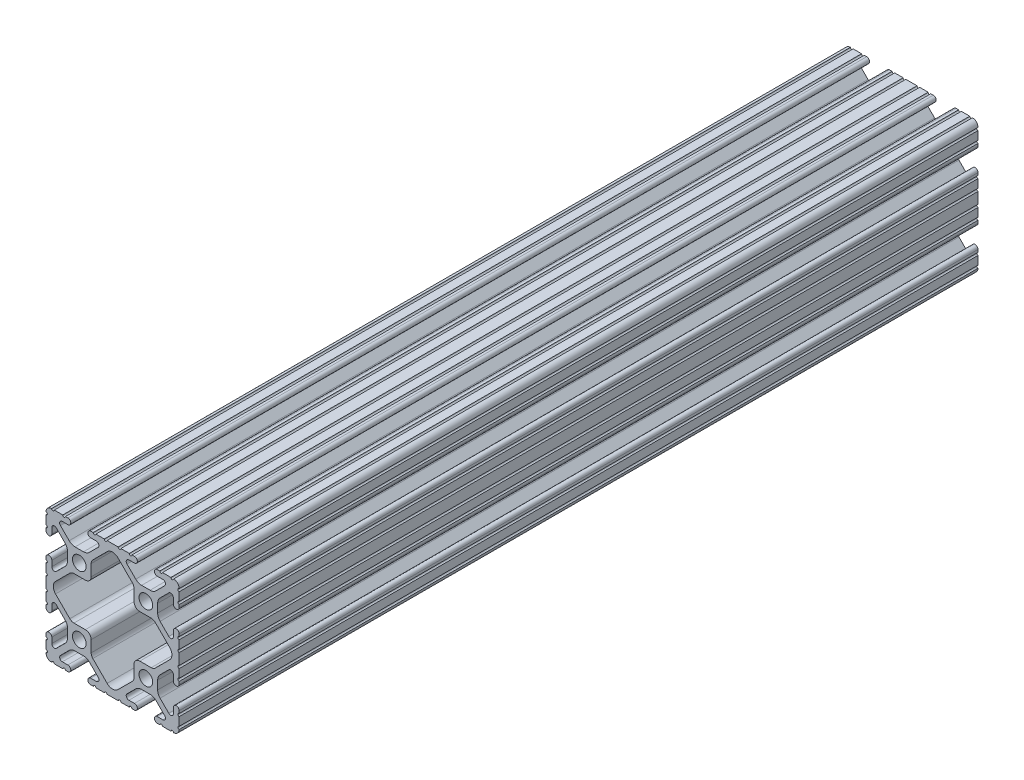
SolidWorks part; units mm, degrees
ref_plane "Front Plane" through (0, 0, 0) normal (0, 0, 1) x (1, 0, 0)
ref_plane "Top Plane" through (0, 0, 0) normal (0, 1, 0) x (1, 0, 0)
ref_plane "Right Plane" through (0, 0, 0) normal (1, 0, 0) x (0, 0, -1)
sketch "Sketch1" plane through (0, 0, 0) normal (0, 0, 1) x (1, 0, 0)
  line L0 (-25.4, 0) -> (25.4, 0) construction
  line L1 (0, 25.4) -> (0, -25.4) construction
  line L2 (-12.7, 12.7) -> (-25.4, 25.4) construction
  line L3 (-25.4, 23.8374) -> (-15.1482, 13.5857) construction
  line L4 (-23.8374, 25.4) -> (-13.5857, 15.1482) construction
  line L5 (9.4488, 25.4) -> (15.9512, 25.4) construction
  line L6 (12.7, 25.4) -> (12.7, 17.1958) construction
  line L7 (5.2832, 23.1902) -> (20.1168, 23.1902) construction
  circle A0 centre (-12.7, 12.7) radius 2.6035 construction
  circle A1 centre (12.7, 12.7) radius 2.6035 construction
  circle A2 centre (12.7, -12.7) radius 2.6035 construction
  circle A3 centre (-12.7, -12.7) radius 2.6035 construction
  circle A4 centre (0, 0) radius 12.4841 construction
  point P4 (0, 0)
  point P8 (0, 0)
  point P26 (12.7, 25.4)
  point P28 (12.7, 23.1902)
  dimension "Center Hole Diameter" = 5.207
  dimension "D5" = 24.9682
  dimension "Rail Width" = 50.8
  dimension "Rail Height" = 50.8
  dimension "D1" = 25.4
  dimension "D2" = 25.4
  dimension "D3" = 2.2098
  dimension "T Slot Width" = 6.5024
  dimension "T Slot Depth" = 8.2042
  dimension "Thickness" = 2.2098
  dimension "D4" = 14.8336
sketch "Sketch2" plane through (0, 0, 0) normal (1, 0, 0) x (0, 0, -1)
  line L0 (152.4, 0) -> (-152.4, 0)
  point P0 (-101.6, 0)
  point P4 (0, 0)
  point P5 (101.6, 0)
  point P6 (152.4, 25.4)
  point P7 (-152.4, 25.4)
  dimension "Length" = 304.8
  dimension "D2" = 50.8
sketch "Sketch3" plane through (0, 0, 0) normal (0, 0, 1) x (1, 0, 0)
  line L0 (-25.4, 0) -> (-25.4, 8.3439)
  line L2 (-23.1902, 8.3439) -> (-23.1902, 6.2252)
  line L3 (-21.4558, 5.5068) -> (-18.1257, 8.8368)
  line L4 (-17.1958, 11.0819) -> (-17.1958, 14.3181)
  line L5 (-18.1257, 16.5632) -> (-21.4558, 19.8932)
  line L6 (-23.1902, 19.1748) -> (-23.1902, 17.0561)
  line L8 (-25.4, 17.0561) -> (-25.4, 23.2918)
  line L9 (-23.2918, 25.4) -> (-17.0561, 25.4)
  line L11 (-17.0561, 23.1902) -> (-19.1748, 23.1902)
  line L12 (-19.8932, 21.4558) -> (-16.5632, 18.1257)
  line L13 (-14.3181, 17.1958) -> (-11.0819, 17.1958)
  line L14 (-8.8368, 18.1257) -> (-5.5068, 21.4558)
  line L15 (-6.2252, 23.1902) -> (-8.3439, 23.1902)
  line L17 (-8.3439, 25.4) -> (0, 25.4)
  line L18 (0, 25.4) -> (0, 22.6275)
  line L19 (-2.0655, 21.772) -> (-7.5331, 16.3043)
  line L20 (-8.1804, 14.7417) -> (-8.1804, 10.3902)
  line L21 (-10.3902, 8.1804) -> (-14.7417, 8.1804)
  line L22 (-16.3043, 7.5331) -> (-21.772, 2.0655)
  line L23 (-22.6275, 0) -> (-25.4, 0)
  line L24 (0, 25.4) -> (0, -25.4) construction
  line L25 (-12.7, 12.7) -> (-25.4, 25.4) construction
  line L26 (-25.4, 0) -> (25.4, 0) construction
  line L27 (5.2832, 23.1902) -> (20.1168, 23.1902) construction
  line L28 (-9.4488, 24.2951) -> (-15.9512, 24.2951) construction
  line L30 (9.4488, 25.4) -> (15.9512, 25.4) construction
  line L31 (-23.8374, 25.4) -> (-13.5857, 15.1482) construction
  line L32 (-25.4, 23.8374) -> (-15.1482, 13.5857) construction
  arc A0 (-7.5331, 16.3043) -> (-8.1804, 14.7417) centre (-5.9706, 14.7417) ccw
  circle A1 centre (-12.7, 12.7) radius 2.6035 construction
  circle A2 centre (-12.7, 12.7) radius 2.6035
  arc A3 (-8.1804, 10.3902) -> (-10.3902, 8.1804) centre (-10.3902, 10.3902) cw
  arc A4 (-14.7417, 8.1804) -> (-16.3043, 7.5331) centre (-14.7417, 5.9706) ccw
  arc A5 (-21.772, 2.0655) -> (-22.6275, 0) centre (-19.7065, 0) ccw
  arc A6 (0, 22.6275) -> (-2.0655, 21.772) centre (0, 19.7065) ccw
  circle A7 centre (0, 0) radius 12.4841 construction
  arc A8 (-17.0561, 23.1902) -> (-17.0561, 25.4) centre (-17.0561, 24.2951) ccw
  arc A9 (-8.3439, 25.4) -> (-8.3439, 23.1902) centre (-8.3439, 24.2951) ccw
  arc A10 (-25.4, 17.0561) -> (-23.1902, 17.0561) centre (-24.2951, 17.0561) ccw
  arc A11 (-23.1902, 8.3439) -> (-25.4, 8.3439) centre (-24.2951, 8.3439) ccw
  arc A12 (-25.4, 23.2918) -> (-23.2918, 25.4) centre (-23.2918, 23.2918) cw
  arc A13 (-5.5068, 21.4558) -> (-6.2252, 23.1902) centre (-6.2252, 22.1742) ccw
  arc A14 (-19.1748, 23.1902) -> (-19.8932, 21.4558) centre (-19.1748, 22.1742) ccw
  arc A15 (-21.4558, 19.8932) -> (-23.1902, 19.1748) centre (-22.1742, 19.1748) ccw
  arc A16 (-21.4558, 5.5068) -> (-23.1902, 6.2252) centre (-22.1742, 6.2252) cw
  arc A17 (-8.8368, 18.1257) -> (-11.0819, 17.1958) centre (-11.0819, 20.3708) cw
  arc A18 (-14.3181, 17.1958) -> (-16.5632, 18.1257) centre (-14.3181, 20.3708) cw
  arc A19 (-18.1257, 16.5632) -> (-17.1958, 14.3181) centre (-20.3708, 14.3181) cw
  arc A20 (-17.1958, 11.0819) -> (-18.1257, 8.8368) centre (-20.3708, 11.0819) cw
  point P37 (-12.7, 24.2951)
  point P87 (-17.1958, 12.7)
  dimension "D1" = 2.2098
  dimension "D2" = 2.921
  dimension "D3" = 2.1082
  dimension "D4" = 1.016
  dimension "D5" = 3.175
  dimension "D6" = 2.2098
extrude "Boss-Extrude1" add sketch "Sketch3" along normal up to vertex (152.4 mm away) and the other way up to vertex (152.4 mm away) up to point (0, 0, 152.4) other way up to point (0, 0, -152.4)
sketch "Sketch4" plane through (0, 0, 152.4) normal (0, 0, 1) x (1, 0, 0)
  line L0 (-12.7, 12.7) -> (-25.4, 25.4) construction
  line L1 (-12.7, 12.7) -> (-25.4, 25.4) construction
  line L2 (-12.7, 12.7) -> (-25.4, 12.7) construction
  circle A0 centre (-25.4, 2.6416) radius 0.508
  circle A1 centre (-25.4, 6.8834) radius 0.508
  circle A2 centre (-25.4, 18.5166) radius 0.508
  circle A3 centre (-25.4, 22.7584) radius 0.508
  circle A4 centre (-22.7584, 25.4) radius 0.508
  circle A5 centre (-18.5166, 25.4) radius 0.508
  circle A6 centre (-6.8834, 25.4) radius 0.508
  circle A7 centre (-2.6416, 25.4) radius 0.508
  dimension "D1" = 1.016
  dimension "D2" = 2.6416
  dimension "D3" = 4.2418
extrude "Cut-Extrude1" cut sketch "Sketch4" against normal through all
pattern_circular "CirPattern1" count 4 over 360 about axis through (0, 0, -152.4) along (0, 0, 1) reverse direction yes of bodies 105
combine bodies "Combine1" bodies to combine 105 108 107 106
sketch "Sketch5" plane through (0, 0, 0) normal (0, 0, 1) x (1, 0, 0)
  circle A2 centre (-12.7, -12.7) radius 2.6035 construction
  circle A3 centre (-12.7, -12.7) radius 2.6035
  arc A4 (8.3439, -25.4) -> (8.3439, -23.1902) centre (8.3439, -24.2951) ccw construction
  arc A5 (8.3439, -25.4) -> (8.3439, -23.1902) centre (8.3439, -24.2951) ccw
  arc A6 (17.0561, -23.1902) -> (17.0561, -25.4) centre (17.0561, -24.2951) ccw construction
  arc A7 (17.0561, -23.1902) -> (17.0561, -25.4) centre (17.0561, -24.2951) ccw
  arc A8 (14.3181, 17.1958) -> (16.5632, 18.1257) centre (14.3181, 20.3708) ccw construction
  arc A9 (14.3181, 17.1958) -> (16.5632, 18.1257) centre (14.3181, 20.3708) ccw
  point P0 (-25.4, 25.4)
  point P1 (-25.4, -25.4)
  point P3 (25.4, 25.4)
  point P4 (25.4, -25.4)
  point P5 (-15.3035, -12.7)
  point P11 (-10.0965, -12.7)
  point P13 (15.9512, -24.2951)
  point P19 (9.4488, -24.2951)
  point P24 (14.3181, 17.1958)
sketch "Sketch6" plane through (0, 0, 0) normal (1, 0, 0) x (0, 0, -1)
  point P0 (-152.4, 25.4)
  point P1 (-101.6, 0)
  point P3 (101.6, 0)
  point P5 (152.4, 25.4)
equation "\"D2@Sketch1\"=\"D1@Sketch1\""
equation "\"D1@Sketch2\"=\"Rail Width@Sketch1\""
equation "\"D2@Sketch2\"=\"D1@Sketch2\""
equation "\"D6@Sketch3\"=\"Thickness@Sketch1\""
